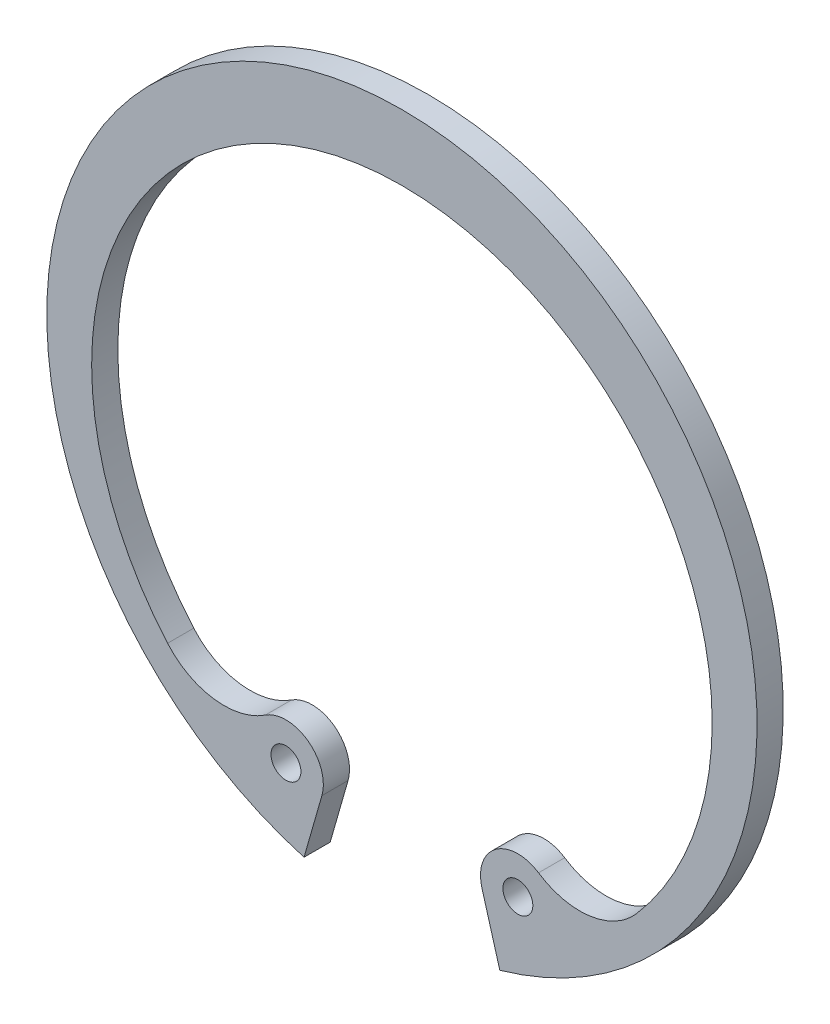
SolidWorks part; units mm, degrees
ref_plane "Front Plane" through (0, 0, 0) normal (0, 0, 1) x (1, 0, 0)
ref_plane "Top Plane" through (0, 0, 0) normal (0, 1, 0) x (1, 0, 0)
ref_plane "Right Plane" through (0, 0, 0) normal (1, 0, 0) x (0, 0, -1)
sketch "Sketch2" plane through (0, 0, 0) normal (0, 0, 1) x (1, 0, 0)
  line L0 (0, 0) -> (0, -23.75) construction
  line L1 (0, 0) -> (6.5464, -22.83)
  line L2 (0, 0) -> (-6.5464, -22.83)
  circle A0 centre (0, 0) radius 23.75
  circle A1 centre (0, -1.4) radius 20.75
  circle A6 centre (-7.7551, -17.9755) radius 2.5
  circle A7 centre (-11.896, -11.7222) radius 5
  circle A9 centre (0, -1.4) radius 15.8
  circle A10 centre (-7.7551, -17.9755) radius 1
  circle A11 centre (7.7551, -17.9755) radius 1
  circle A12 centre (7.7551, -17.9755) radius 2.5
  circle A13 centre (11.896, -11.7222) radius 5
  dimension "D1" = 47.5
  dimension "D5" = 41.5
  dimension "D2" = 10
  dimension "D6" = 5
  dimension "D7" = 31.6
  dimension "D8" = 2
  dimension "D3" = 32
  dimension "D4" = 1.4
extrude "Boss-Extrude1" add sketch "Sketch2" along normal blind 1.75 contours A7 A1 A6 | A1 A6 A10 | A1 A12 L1 A0 L2 A6 | A6 A1 L2 | A1 A12 L1 | A12 A1 A11 | A1 A13 A12 | A1 A6 | A12 A1 | A6 | A10 region at (6.4973, -20.4603, 0) region at (5.5439, -16.9695, 0) region at (-6.4973, -20.4603, 0) region at (-6.5193, -20.0669, 0) region at (7.4431, -21.4802, 0) region at (8.8013, -20.2115, 0) region at (11.5841, -17.558, 0) region at (-8.8013, -20.2115, 0) region at (-11.5841, -17.558, 0)
equation "\"D1@Sketch2\" = \"G_anneau_alesage_rouleau\""
equation "\"c_anneau\"=31.6"
equation "\"D5@Sketch2\" = \"G_anneau_alesage_rouleau\" - 6"
equation "\"e_anneau\"=1.75"
equation "\"D2@Sketch2\"=2*\"D6@Sketch2\""
equation "\"D7@Sketch2\"=\"c_anneau\""
equation "\"d_ext_rouleau\"= 90"
equation "\"epaisseur_rouleau\"=80"
equation "\"alesage-rouleau\"= 52"
equation "\"jeu_dent_rouleau\"= 2"
equation "\"profondeur_dent_rouleau\"=4"
equation "\"n_dent_roueau\"= 15"
equation "\"d_ext_roulement_rouleau\"= 42"
equation "\"d_int_roulement_rouleau\"= 20"
equation "\"B_roulement_rouleau\"= 12"
equation "\"r_roulement_rouleau\"= 0.6"
equation "\"d_bille_roulement_rouleau\"= 8"
equation "\"F_anneau_alesage_rouleau\"=1.85"
equation "\"G_anneau_alesage_rouleau\"=47.5"
equation "\"K_anneau_alesage_rouleau\"=3.75"
equation "\"d_vis_flasque_rouleau\"=5"
equation "\"l-x_vis_flasque_rouleau\"=4"
equation "\"g_anneau_arbre_rouleau\"=19"
equation "\"f_anneau_arbre_rouleau\"=1.3"
equation "\"k_anneau_arbre_rouleau\"=1.5"
equation "\"h_matrice\"= 18"
equation "\"d_matrice\"= 220"
equation "\"d_granulat\"= 8"
equation "\"zone_vide_matrice\" = 48"
equation "\"d_alesage_matrice\"=20"
equation "\"a_clavette_alesage_matrice\"=6"
equation "\"entrax_vis_rouleau\"=65"
